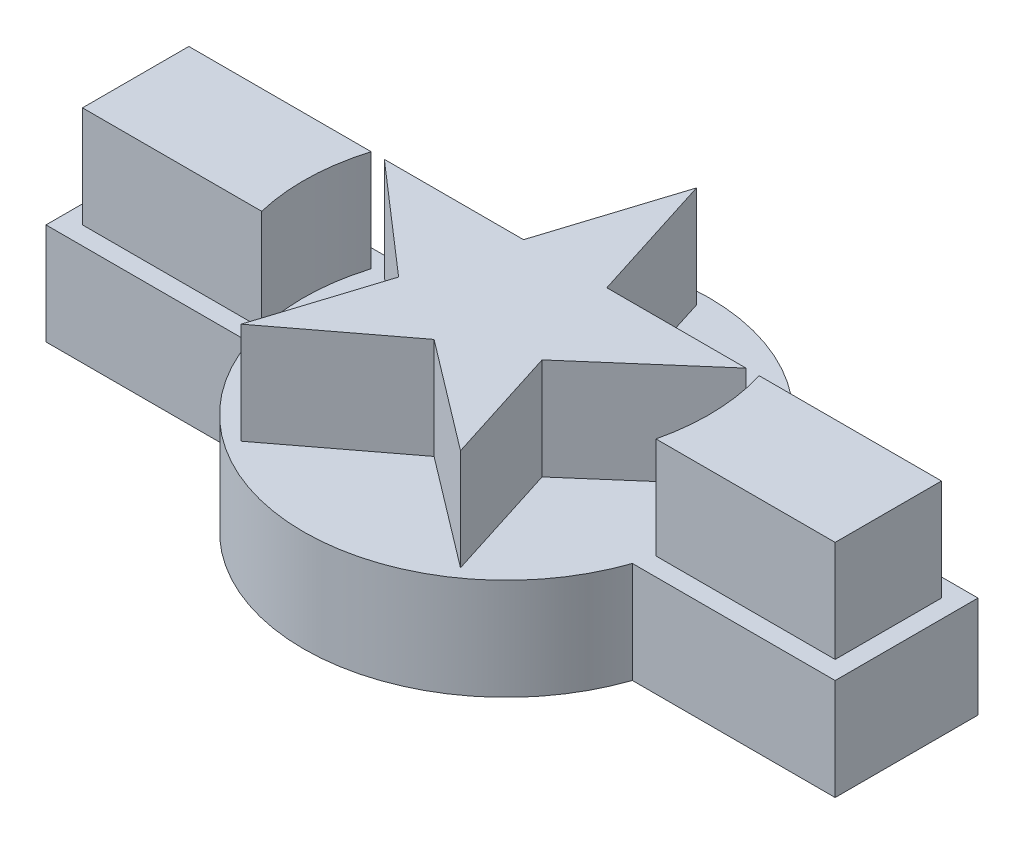
SolidWorks part; units mm, degrees
ref_plane "Plan de face" through (0, 0, 0) normal (0, 0, 1) x (1, 0, 0)
ref_plane "Plan de dessus" through (0, 0, 0) normal (0, 1, 0) x (1, 0, 0)
ref_plane "Plan de droite" through (0, 0, 0) normal (1, 0, 0) x (0, 0, -1)
sketch "Sketch2" plane through (0, 0, 0) normal (0, 1, 0) x (1, 0, 0)
  circle A0 centre (0, 0) radius 5
  dimension "D1" = 10
sketch "Sketch1" plane through (0, 0, 0) normal (0, 1, 0) x (1, 0, 0)
  line L0 (4.7622, 14.7032) -> (23.811, 14.7032) construction
  line L1 (81.1379, 215.2075) -> (534.4712, 215.2075) construction
sketch "Sketch3" plane through (0, 0, 0) normal (0, 1, 0) x (1, 0, 0)
  line L0 (9.7303, 1.9028) -> (9.7303, -1.6198)
  line L1 (9.7303, -1.6198) -> (4.7303, -1.6198)
  line L2 (9.7303, 1.9028) -> (4.6238, 1.9028)
  line L3 (0, -5) -> (0, 5)
  line L4 (9.2803, 1.4528) -> (9.2803, -1.1698)
  line L5 (9.2803, -1.1698) -> (4.8612, -1.1698)
  line L6 (9.2803, 1.4528) -> (4.7843, 1.4528)
  line L7 (0, 4.69) -> (1.0269, 1.4528)
  line L8 (1.0269, 1.4528) -> (4.4593, 1.4528)
  line L9 (4.4593, 1.4528) -> (1.7688, -0.8861)
  line L10 (1.7688, -0.8861) -> (2.7035, -3.8324)
  line L11 (2.7035, -3.8324) -> (0, -1.7804)
  circle A0 centre (0, 0) radius 5 construction
  arc A1 (0, -5) -> (0, 5) centre (0, 0) ccw
  point P15 (1.7587, -0.8515)
  point P20 (0, 4.6908)
  point P21 (0, -1.72)
  dimension "D1" = 3.5226
  dimension "D2" = 5
  dimension "D3" = 1.9028
  dimension "D4" = 0.45
  dimension "D5" = 0.45
  dimension "D6" = 0.45
  dimension "D7" = 17.6
  dimension "D8" = 0.31
  dimension "D9" = 4.69
  dimension "D10" = 4.69
  dimension "D11" = 35.2
  dimension "D12" = 4.69
  dimension "D13" = 41
extrude "Boss-Extrude1" add sketch "Sketch3" along normal blind 5 contours L11 L10 L9 L8 L7 L3 | A1 L5 L4 L6 region at (7.1098, 0, -0.1453) region at (1.3784, 0, -0.0009)
extrude "Boss-Extrude2" add sketch "Sketch3<3>" along normal blind 2.5 contours L3 A1 L7 L8 L9 L10 L11 | A1 L1 L0 L2 L6 L4 L5 region at (9.6683, 0, -0.1415) region at (4.6041, 0, -1.6421)
sketch "Sketch3<3>" plane through (0, 0, 0) normal (0, 1, 0) x (1, 0, 0) same geometry as "Sketch3"
mirror "Mirror1" about plane through (0, 0, 0) normal (1, 0, 0) of bodies 103
equation "\"D5@Sketch3\"=\"D4@Sketch3\""
equation "\"D6@Sketch3\"=\"D4@Sketch3\""
equation "\"D10@Sketch3\"=\"D9@Sketch3\""
equation "\"D11@Sketch3\"=\"D7@Sketch3\"*2"
equation "\"D12@Sketch3\"=\"D9@Sketch3\""
